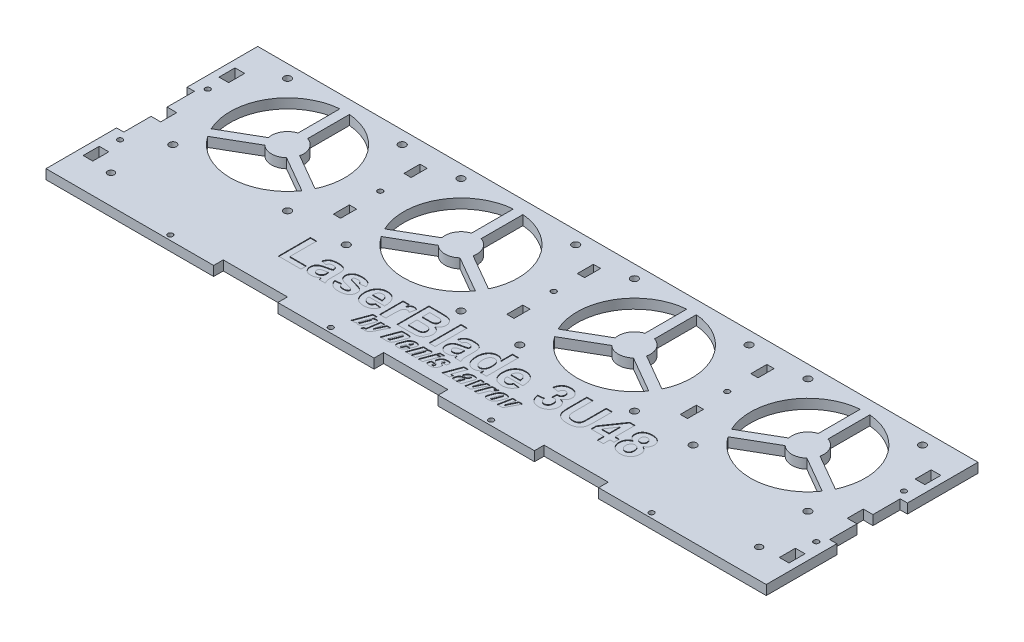
SolidWorks part; units mm, degrees
ref_plane "Front Plane" through (0, 0, 0) normal (0, 0, 1) x (1, 0, 0)
ref_plane "Top Plane" through (0, 0, 0) normal (0, 1, 0) x (1, 0, 0)
ref_plane "Right Plane" through (0, 0, 0) normal (1, 0, 0) x (0, 0, -1)
sketch "Sketch1" plane through (0, 0, 0) normal (0, 1, 0) x (1, 0, 0)
  line L1 (-224.5, -66) -> (224.5, -66)
  line L2 (-224.5, -66) -> (-224.5, 66)
  line L3 (-224.5, 66) -> (224.5, 66)
  line L4 (224.5, -66) -> (224.5, 66)
  line L5 (-224.5, -66) -> (224.5, 66) construction
  line L6 (-224.5, 66) -> (224.5, -66) construction
  line L7 (-220, -66) -> (220, -66) construction
  line L8 (-220, -66) -> (-220, 66) construction
  line L9 (-220, 66) -> (220, 66) construction
  line L10 (220, -66) -> (220, 66) construction
  line L11 (-220, -66) -> (220, 66) construction
  line L12 (-220, 66) -> (220, -66) construction
  point P0 (0, 0)
  point P6 (0, 0)
  dimension "D1" = 449
  dimension "D2" = 132
  dimension "D3" = 440
extrude "Boss-Extrude1" add sketch "Sketch1" along normal blind 6
sketch "Sketch3" plane through (0, 6, 0) normal (0, 1, 0) x (1, 0, 0)
  line L0 (-220, -66) -> (-220, 66) construction
  line L1 (220, -66) -> (220, 66) construction
  line L2 (-220, -66) -> (-220, 66) construction
  line L3 (220, -66) -> (220, 66) construction
  line L4 (-220, 63) -> (220, 63) construction
  line L5 (-224.5, 66) -> (224.5, 66) construction
  line L6 (-214, -66) -> (-214, 66) construction
  line L8 (214, -66) -> (214, 66) construction
  line L9 (-224.5, -66) -> (224.5, -66) construction
  line L13 (-224.5, -66) -> (224.5, -66)
  line L14 (-224.5, -60) -> (224.5, -60) construction
  line L15 (-214, -17) -> (214, -17) construction
  dimension "D1" = 3
  dimension "D5" = 80
  dimension "D2" = 6
  dimension "D3" = 6
  dimension "D4" = 6
sketch "Sketch4" plane through (0, 6, 0) normal (0, 1, 0) x (1, 0, 0)
  line L0 (-220, -66) -> (-220, 66) construction
  line L1 (-220, 47.3321) -> (-214, 47.3321)
  line L2 (-220, 47.3321) -> (-220, 37.3321)
  line L3 (-220, 37.3321) -> (-214, 37.3321)
  line L4 (-214, 47.3321) -> (-214, 37.3321)
  line L5 (-214, -66) -> (-214, 66) construction
  line L11 (-220, 5) -> (-220, -5)
  line L12 (-220, -5) -> (-214, -5)
  line L13 (-214, 5) -> (-214, -5)
  line L14 (-220, 5) -> (-214, 5)
  line L19 (-220, -37.3321) -> (-220, -47.3321)
  line L20 (-220, -47.3321) -> (-214, -47.3321)
  line L21 (-214, -37.3321) -> (-214, -47.3321)
  line L22 (-220, -37.3321) -> (-214, -37.3321)
  line L23 (-220, 47.3321) -> (-220, 66) construction
  line L24 (-220, -47.3321) -> (-220, -66) construction
  line L25 (-220, 26.1661) -> (-220, 16.1661) [skipped]
  line L26 (-220, 16.1661) -> (-214, 16.1661) [skipped]
  line L27 (-214, 26.1661) -> (-214, 16.1661) [skipped]
  line L28 (-220, 26.1661) -> (-214, 26.1661) [skipped]
  line L29 (-220, -16.1661) -> (-220, -26.1661) [skipped]
  line L30 (-220, -26.1661) -> (-214, -26.1661) [skipped]
  line L31 (-214, -16.1661) -> (-214, -26.1661) [skipped]
  line L32 (-220, -16.1661) -> (-214, -16.1661) [skipped]
  dimension "D1" = 10
  dimension "D2" = 5
extrude "Cut-Extrude2" cut sketch "Sketch4" against normal through all
sketch "Sketch5" plane through (0, 6, 0) normal (0, 1, 0) x (1, 0, 0)
  line L0 (-217, -27.3321) -> (-217, -37.3321) construction
  line L1 (-214, -37.3321) -> (-220, -37.3321) construction
  line L2 (-217, 27.3321) -> (-217, 37.3321) construction
  line L3 (-220, 37.3321) -> (-214, 37.3321) construction
  circle A0 centre (-217, -27.3321) radius 1.6
  circle A1 centre (-217, 27.3321) radius 1.6
  dimension "D1" = 3.2
  dimension "D2" = 10
extrude "Cut-Extrude3" cut sketch "Sketch5" against normal up to next
mirror "Mirror1" about plane through (0, 0, 0) normal (1, 0, 0) of "Cut-Extrude3", "Cut-Extrude2"
sketch "Sketch6" plane through (0, 6, 0) normal (0, 1, 0) x (1, 0, 0)
  line L1 (-110.375, -1) -> (-110.375, -14) construction
  line L2 (-220, 58) -> (220, 58)
  line L3 (-220, 58) -> (220, 58) construction
  line L4 (-197.9375, 58) -> (-126.4375, 58) construction
  line L5 (-197.9375, 58) -> (-197.9375, -13.5) construction
  line L6 (-197.9375, -13.5) -> (-126.4375, -13.5) construction
  line L7 (-126.4375, 58) -> (-126.4375, -13.5) construction
  line L8 (-110.375, -1) -> (-110.375, -14) construction
  line L9 (-214, 25.7321) -> (-214, 5) construction
  line L10 (-214, 25.7321) -> (-214, 5) construction
  line L11 (-214, 15.3661) -> (-197.9375, 15.3661) construction
  line L12 (-126.4375, 22.25) -> (-110.375, 22.25) construction
  circle A0 centre (-197.9375, 58) radius 2.25
  circle A1 centre (-126.4375, 58) radius 2.25
  circle A2 centre (-126.4375, -13.5) radius 2.25
  circle A3 centre (-197.9375, -13.5) radius 2.25
  dimension "D3" = 4.5
  dimension "D2" = 71.5
  dimension "D1" = 5
extrude "Cut-Extrude4" cut sketch "Sketch6" against normal up to next
pattern_linear "LPattern1" count 4 spacing 108.125 along (1, 0, 0) of "Cut-Extrude4"
sketch "Sketch7" plane through (0, 6, 0) normal (0, 1, 0) x (1, 0, 0)
  line L0 (224.5, 66) -> (-224.5, 66) construction
  line L1 (-105.875, -14) -> (-110.375, -14) construction
  line L5 (-108.125, 66) -> (-108.125, -14) construction
  line L7 (-110.375, 53) -> (-105.875, 53)
  line L8 (-110.375, 53) -> (-110.375, 43)
  line L9 (-110.375, 43) -> (-105.875, 43)
  line L10 (-105.875, 53) -> (-105.875, 43)
  line L11 (-110.375, 53) -> (-105.875, 43) construction
  line L12 (-110.375, 43) -> (-105.875, 53) construction
  line L13 (-108.125, 26) -> (-78.5339, 26) construction
  line L14 (-110.375, 9) -> (-105.875, -1) construction
  line L15 (-110.375, -1) -> (-105.875, 9) construction
  line L16 (-105.875, -1) -> (-105.875, 9)
  line L17 (-110.375, 9) -> (-105.875, 9)
  line L18 (-110.375, -1) -> (-110.375, 9)
  line L19 (-110.375, -1) -> (-105.875, -1)
  line L20 (-105.875, -14) -> (-110.375, -14) construction
  circle A0 centre (-108.125, 26) radius 1.6
  point P12 (-108.125, 48)
  point P27 (-108.125, 4)
  dimension "D3" = 3.2
  dimension "D1" = 10
  dimension "D4" = 4.5
extrude "Cut-Extrude5" cut sketch "Sketch7" against normal up to next
sketch "Sketch8" plane through (0, 6, 0) normal (0, 1, 0) x (1, 0, 0)
  line L0 (-197.9375, 58) -> (-126.4375, -13.5) construction
  line L1 (-162.1875, 22.25) -> (-162.1875, 58) construction
  line L2 (-159.1875, 31.7894) -> (-159.1875, 57.8739)
  line L3 (-165.1875, 31.7894) -> (-165.1875, 57.8739)
  line L4 (-159.1875, 22.25) -> (-159.1875, 58) construction
  line L5 (-165.1875, 22.25) -> (-165.1875, 58) construction
  line L6 (-155.4261, 14.8822) -> (-132.8363, 1.84)
  line L7 (-152.4261, 20.0784) -> (-129.8363, 7.0361)
  line L8 (-171.9489, 20.0784) -> (-194.5387, 7.0361)
  line L9 (-168.9489, 14.8822) -> (-191.5387, 1.84)
  arc A0 (-165.1875, 31.7894) -> (-171.9489, 20.0784) centre (-162.1875, 22.25) ccw
  arc A1 (-165.1875, 57.8739) -> (-194.5387, 7.0361) centre (-162.1875, 22.25) ccw
  arc A2 (-152.4261, 20.0784) -> (-159.1875, 31.7894) centre (-162.1875, 22.25) ccw
  arc A3 (-168.9489, 14.8822) -> (-155.4261, 14.8822) centre (-162.1875, 22.25) ccw
  arc A4 (-129.8363, 7.0361) -> (-159.1875, 57.8739) centre (-162.1875, 22.25) ccw
  arc A5 (-191.5387, 1.84) -> (-132.8363, 1.84) centre (-162.1875, 22.25) ccw
  point P0 (-164.1875, 22.8125)
  point P6 (-197.9375, 22.25)
  point P24 (-162.1875, 22.25)
  dimension "D1" = 20
  dimension "D2" = 3
  dimension "D3" = 3
extrude "Cut-Extrude6" cut sketch "Sketch8" against normal up to next
pattern_linear "LPattern2" count 4 spacing 108.125 along (1, 0, 0) of "Cut-Extrude6"
pattern_linear "LPattern3" count 3 spacing 108.125 along (1, 0, 0) of "Cut-Extrude5"
sketch "Sketch10" plane through (0, 6, 0) normal (0, 1, 0) x (1, 0, 0)
  line L0 (18.3125, -13.5) -> (18.3125, -66) construction
  line L2 (-224.5, -66) -> (224.5, -66) construction
  line L3 (-224.5, -39.75) -> (224.5, -39.75) construction
  line L5 (-224.5, 66) -> (-224.5, -66) construction
  line L6 (224.5, -66) -> (224.5, 66) construction
  line L7 (-224.5, -40.75) -> (224.5, -40.75) construction
  line L8 (-224.5, -52.75) -> (224.5, -52.75) construction
  text T0 "<b>LaserBlade 3U48</b>" font "Arial" height 20
  text T1 "<i>by Denis Lavrov</i>" font "Impact" height 10
  point P12 (18.3125, -39.75)
  dimension "D1" = 1
  dimension "D2" = 12
extrude "Cut-Extrude8" cut sketch "Sketch10" against normal blind 0.4
sketch "Sketch11" plane through (0, 6, 0) normal (0, 1, 0) x (1, 0, 0)
  line L0 (-224.5, -63) -> (224.5, -63) construction
  line L1 (-224.5, 66) -> (-224.5, -66) construction
  line L2 (224.5, -66) -> (224.5, 66) construction
  line L3 (-224.5, -66) -> (224.5, -66) construction
  line L4 (0, -63) -> (0, -96.6192) construction
  circle A0 centre (50, -63) radius 1.6
  circle A1 centre (150, -63) radius 1.6
  circle A2 centre (-50, -63) radius 1.6
  circle A3 centre (-150, -63) radius 1.6
  dimension "D3" = 3.2
  dimension "D1" = 3
  dimension "D2" = 100
  dimension "D4" = 2
extrude "Cut-Extrude9" cut sketch "Sketch11" against normal up to next
sketch "Sketch12" plane through (0, 6, 0) normal (0, 1, 0) x (1, 0, 0)
  line L0 (-120, -66) -> (-80, -66) construction
  line L1 (-80, -66) -> (-80, -60) construction
  line L2 (-80, -60) -> (-120, -60) construction
  line L3 (-120, -60) -> (-120, -66) construction
  line L4 (-20, -66) -> (20, -66) construction
  line L5 (20, -66) -> (20, -60) construction
  line L6 (20, -60) -> (-20, -60) construction
  line L7 (-20, -60) -> (-20, -66) construction
  line L8 (80, -66) -> (120, -66) construction
  line L9 (120, -66) -> (120, -60) construction
  line L10 (120, -60) -> (80, -60) construction
  line L11 (80, -60) -> (80, -66) construction
  line L12 (-120, -66) -> (-80, -66)
  line L13 (-80, -66) -> (-80, -60)
  line L14 (-80, -60) -> (-120, -60)
  line L15 (-120, -60) -> (-120, -66)
  line L16 (-20, -66) -> (20, -66)
  line L17 (20, -66) -> (20, -60)
  line L18 (20, -60) -> (-20, -60)
  line L19 (-20, -60) -> (-20, -66)
  line L20 (80, -66) -> (120, -66)
  line L21 (120, -66) -> (120, -60)
  line L22 (120, -60) -> (80, -60)
  line L23 (80, -60) -> (80, -66)
extrude "Cut-Extrude10" cut sketch "Sketch12" against normal up to next
sketch "Sketch13" plane through (0, 6, 0) normal (0, 1, 0) x (1, 0, 0)
  circle A0 centre (202, -48) radius 2.1 construction
  circle A1 centre (202, -48) radius 2.1
  circle A2 centre (-202, -48) radius 2.1 construction
  circle A3 centre (-202, -48) radius 2.1
extrude "Cut-Extrude11" cut sketch "Sketch13" against normal through all
sketch "Sketch14" plane through (0, 6, 0) normal (0, 1, 0) x (1, 0, 0)
  line L0 (-224.5, 0) -> (-220, 0) construction
  line L1 (-224.5, 66) -> (-224.5, -66) construction
  line L2 (-220, 5) -> (-220, -5) construction
  line L3 (-224.5, -22) -> (-220, -22)
  line L4 (-224.5, 22) -> (-220, 22)
  line L5 (-224.5, -22) -> (-224.5, 22)
  line L6 (-220, -22) -> (-220, 22)
  line L7 (220, 0) -> (224.5, 0) construction
  line L8 (220, 5) -> (220, -5) construction
  line L9 (224.5, -66) -> (224.5, 66) construction
  line L10 (220, -22) -> (224.5, -22)
  line L11 (220, 22) -> (224.5, 22)
  line L12 (220, -22) -> (220, 22)
  line L13 (224.5, -22) -> (224.5, 22)
  dimension "D1" = 22
  dimension "D2" = 22
  dimension "D3" = 22
  dimension "D4" = 22
extrude "Cut-Extrude12" cut sketch "Sketch14" against normal through all
